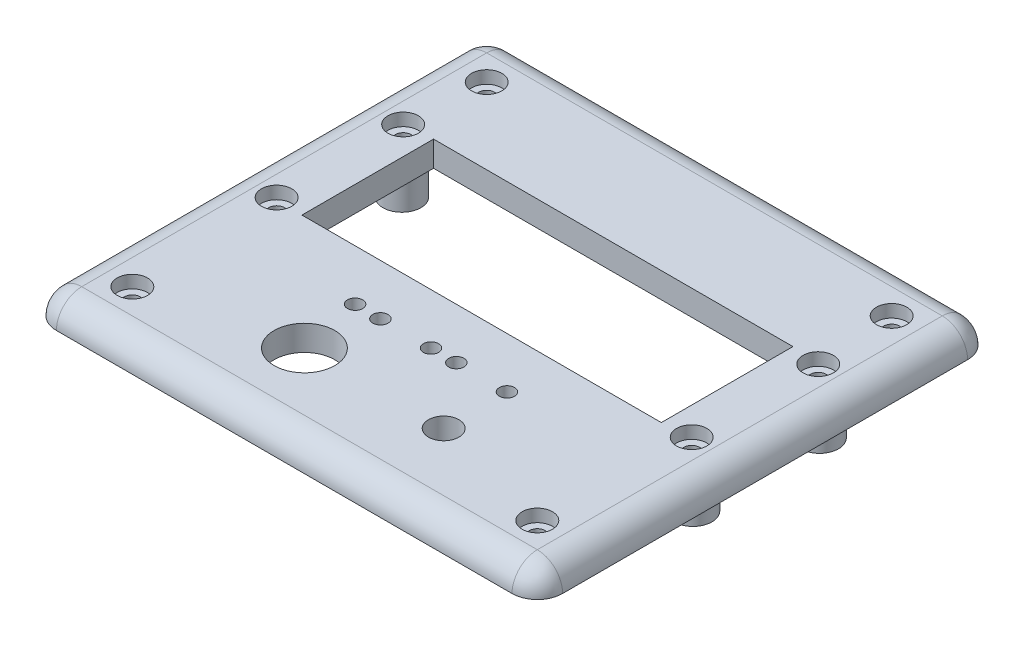
SolidWorks part; units mm, degrees
ref_plane "Front Plane" through (0, 0, 0) normal (0, 0, 1) x (1, 0, 0)
ref_plane "Top Plane" through (0, 0, 0) normal (0, 1, 0) x (1, 0, 0)
ref_plane "Right Plane" through (0, 0, 0) normal (1, 0, 0) x (0, 0, -1)
sketch "Sketch1" plane through (0, 0, 0) normal (0, 1, 0) x (1, 0, 0)
  line L1 (0, 0) -> (100, 0)
  line L2 (0, 0) -> (0, 90)
  line L3 (0, 90) -> (100, 90)
  line L4 (100, 0) -> (100, 90)
  dimension "D1" = 100
  dimension "D2" = 90
extrude "Boss-Extrude1" add sketch "Sketch1" along normal blind 5
fillet "Fillet1" radius 5 4 edges at (0, 2.5, -90) (0, 2.5, 0) (100, 2.5, -90) (100, 2.5, 0)
fillet "Fillet2" radius 5 8 edges at (1.4645, 5, -1.4645) (98.5355, 5, -88.5355) (98.5355, 5, -1.4645) (100, 5, -45) (50, 5, 0) (0, 5, -45) (1.4645, 5, -88.5355) (50, 5, -90)
sketch "Sketch2" plane through (0, 5, 0) normal (0, 1, 0) x (1, 0, 0)
  line L0 (90, 80) -> (10, 80) construction
  line L1 (10, 80) -> (10, 10) construction
  line L2 (10, 80) -> (5, 80) construction
  line L3 (5, 85) -> (5, 5) construction
  line L4 (5, 80) -> (5, 85) construction
  line L5 (90, 10) -> (95, 10) construction
  line L6 (95, 5) -> (95, 85) construction
  line L7 (95, 10) -> (95, 5) construction
  circle A0 centre (10, 80) radius 1.55
  circle A1 centre (10, 10) radius 1.55
  circle A2 centre (90, 10) radius 1.55
  circle A3 centre (90, 80) radius 1.55
  dimension "D1" = 3.1
  dimension "D2" = 80
  dimension "D3" = 70
extrude "Cut-Extrude1" cut sketch "Sketch2" against normal blind 10
sketch "Sketch3" plane through (0, 5, 0) normal (0, 1, 0) x (1, 0, 0)
  circle A0 centre (10, 80) radius 3
  circle A1 centre (90, 80) radius 3
  circle A2 centre (90, 10) radius 3
  circle A3 centre (10, 10) radius 3
  dimension "D1" = 6
extrude "Cut-Extrude2" cut sketch "Sketch3" against normal blind 2.5
sketch "Sketch4" plane through (0, 5, 0) normal (0, 1, 0) x (1, 0, 0)
  line L0 (85.5, 52) -> (95, 52) construction
  line L1 (65, 29) -> (95, 29) construction
  line L3 (95, 5) -> (95, 85) construction
  line L4 (35, 29) -> (5, 29) construction
  line L5 (5, 85) -> (5, 5) construction
  line L6 (14.5, 65) -> (85.5, 65)
  line L7 (14.5, 65) -> (14.5, 39)
  line L8 (14.5, 39) -> (85.5, 39)
  line L9 (85.5, 65) -> (85.5, 39)
  line L10 (14.5, 52) -> (5, 52) construction
  line L11 (95, 85) -> (5, 85) construction
  circle A0 centre (35, 29) radius 1.5
  circle A1 centre (40, 29) radius 1.5
  circle A2 centre (50, 29) radius 1.5
  circle A3 centre (55, 29) radius 1.5
  circle A4 centre (65, 29) radius 1.5
  dimension "D1" = 3
  dimension "D2" = 5
  dimension "D3" = 5
  dimension "D4" = 10
  dimension "D5" = 10
  dimension "D6" = 10
  dimension "D7" = 71
  dimension "D8" = 26
  dimension "D9" = 20
extrude "Cut-Extrude3" cut sketch "Sketch4" against normal through all
sketch "Sketch5" plane through (0, 0, 0) normal (0, -1, 0) x (1, 0, 0)
  line L0 (85.5, -52) -> (92.5, -52) construction
  line L1 (7.5, -37) -> (92.5, -37) construction
  line L2 (7.5, -37) -> (7.5, -67) construction
  line L3 (7.5, -67) -> (92.5, -67) construction
  line L4 (92.5, -37) -> (92.5, -67) construction
  line L5 (85.5, -39) -> (85.5, -65) construction
  line L6 (14.5, -52) -> (7.5, -52) construction
  line L7 (14.5, -65) -> (14.5, -39) construction
  line L8 (9, -39.5) -> (9, -37) construction
  line L9 (9, -64.5) -> (9, -67) construction
  circle A0 centre (9, -39.5) radius 1.5
  circle A1 centre (9, -64.5) radius 1.5
  circle A2 centre (91, -64.5) radius 1.5
  circle A3 centre (91, -39.5) radius 1.5
  dimension "D3" = 3
  dimension "D1" = 85
  dimension "D2" = 30
  dimension "D4" = 25
extrude "Cut-Extrude4" cut sketch "Sketch5" against normal through all
sketch "Sketch8" plane through (0, 0, 0) normal (0, -1, 0) x (1, 0, 0)
  line L0 (95, -90) -> (5, -90) construction
  line L1 (8.75, -39.5) -> (0, -39.5) construction
  line L2 (0, -85) -> (0, -5) construction
  line L5 (100, -5) -> (100, -85) construction
  line L6 (100, -64.5) -> (91.25, -64.5) construction
  circle A4 centre (8.75, -39.5) radius 3.75
  circle A5 centre (91.25, -39.5) radius 3.75
  circle A6 centre (91.25, -64.5) radius 3.75
  circle A7 centre (8.75, -64.5) radius 3.75
  point P8 (91, -39.5)
  dimension "D1" = 7.5
  dimension "D2" = 25
  dimension "D3" = 82.5
  dimension "D4" = 25.5
extrude "Boss-Extrude3" add sketch "Sketch8" along normal blind 7.5
sketch "Sketch6" plane through (0, 5, 0) normal (0, 1, 0) x (1, 0, 0)
  circle A0 centre (9, 39.5) radius 3
  circle A1 centre (9, 64.5) radius 3
  circle A2 centre (91, 64.5) radius 3
  circle A3 centre (91, 39.5) radius 3
  dimension "D1" = 6
extrude "Cut-Extrude5" cut sketch "Sketch6" against normal blind 2.5
sketch "Sketch10" plane through (0, 0, 0) normal (0, 1, 0) x (1, 0, 0)
  circle A0 centre (9, 64.5) radius 1.55
  circle A1 centre (9, 39.5) radius 1.55
  circle A2 centre (91, 39.5) radius 1.55
  circle A3 centre (91, 64.5) radius 1.55
  dimension "D1" = 3.1
extrude "Cut-Extrude7" cut sketch "Sketch10" against normal through all both and the other way through all
sketch "Sketch11" plane through (0, 5, 0) normal (0, 1, 0) x (1, 0, 0)
  line L0 (65, 16.5) -> (65, 29) construction
  line L1 (40, 29) -> (35, 29) construction
  line L2 (37.5, 29) -> (37.5, 16.5) construction
  circle A0 centre (37.5, 16.5) radius 6
  circle A1 centre (65, 16.5) radius 3
  dimension "D1" = 12
  dimension "D2" = 6
  dimension "D3" = 12.5
extrude "Cut-Extrude8" cut sketch "Sketch11" against normal blind 5
